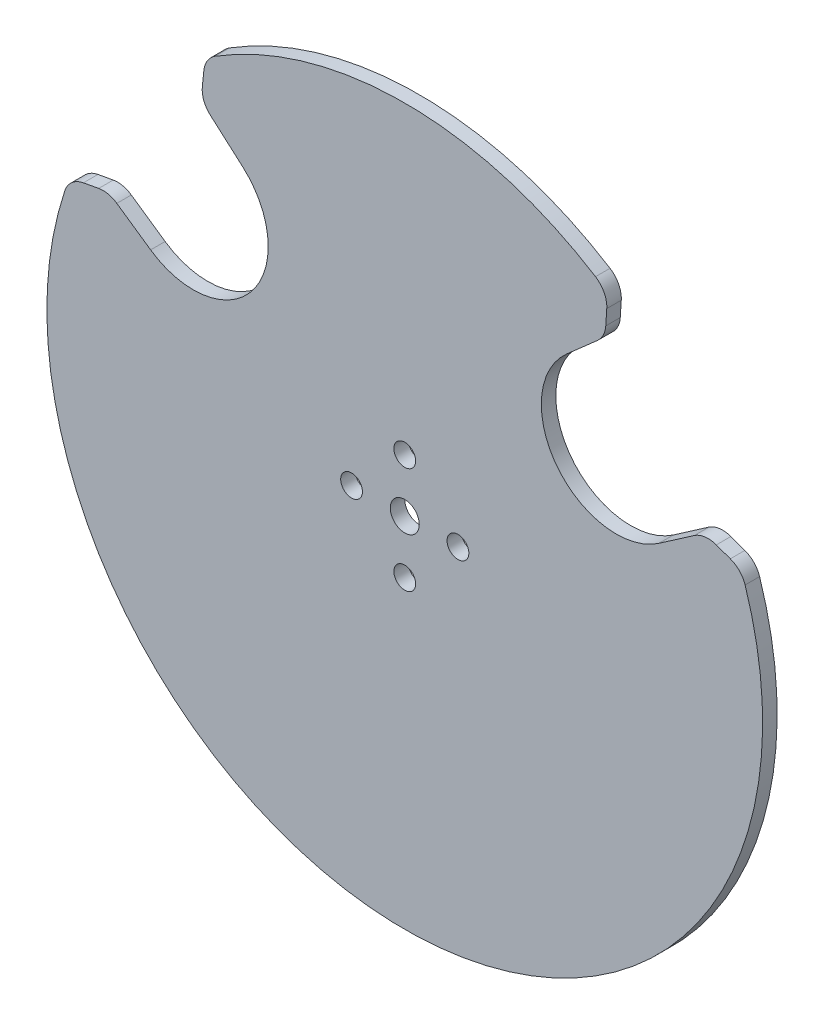
SolidWorks part; units mm, degrees
material "Contreplaqué pin"
ref_plane "Plan de face" through (0, 0, 0) normal (0, 0, 1) x (1, 0, 0)
ref_plane "Plan de dessus" through (0, 0, 0) normal (0, 1, 0) x (1, 0, 0)
ref_plane "Plan de droite" through (0, 0, 0) normal (1, 0, 0) x (0, 0, -1)
sketch "Esquisse1" plane through (0, 0, 0) normal (0, 0, 1) x (1, 0, 0)
  line L0 (0, 0) -> (-43.7346, 34.1692) construction
  line L1 (67.0032, 31.4098) -> (52.5476, 21.4185)
  line L2 (0, 0) -> (0, 74) construction
  line L3 (-43.7346, 34.1692) -> (-58.3128, 45.5589) construction
  line L4 (-46.6863, 57.4142) -> (-33.4947, 45.8051)
  line L5 (-67.0032, 31.4098) -> (-52.5476, 21.4185)
  line L6 (46.6863, 57.4142) -> (33.4947, 45.8051)
  arc A0 (-67.0032, 31.4098) -> (67.0032, 31.4098) centre (0, 0) ccw
  circle A1 centre (0, 0) radius 11 construction
  circle A2 centre (0, 11) radius 2.25
  circle A3 centre (11, 0) radius 2.25
  circle A4 centre (0, -11) radius 2.25
  circle A5 centre (-11, 0) radius 2.25
  arc A7 (-52.5476, 21.4185) -> (-33.4947, 45.8051) centre (-43.7346, 34.1692) ccw
  arc A9 (52.5476, 21.4185) -> (33.4947, 45.8051) centre (43.7346, 34.1692) cw
  arc A10 (46.6863, 57.4142) -> (-46.6863, 57.4142) centre (0, 0) ccw
  circle A15 centre (0, 0) radius 3
  point P27 (67.0032, 31.4098)
  point P30 (46.6863, 57.4142)
  point P33 (-46.6863, 57.4142)
  point P36 (-67.0032, 31.4098)
  dimension "D1" = 74
  dimension "D2" = 22
  dimension "D3" = 4.5
  dimension "D6" = 33
  dimension "D4" = 15.5
  dimension "D11" = 6
  dimension "D5" = 52
  dimension "D7" = 18.5
  dimension "D9" = 3.349
  dimension "D10" = 3.349
extrude "Boss.-Extru.1" add sketch "Esquisse1" along normal blind 3
fillet "Congé1" [suppressed] radius 7
chamfer "Chanfrein1" distance 7 angle 45 4 edges at (67.0032, 31.4098, 1.5) (46.6863, 57.4142, 1.5) (-46.6863, 57.4142, 1.5) (-67.0032, 31.4098, 1.5) first distance on face at (0, -21.2951, 1.5) first distance on face at (40.0905, 51.6096, 1.5) first distance on face at (0, 65.7071, 1.5) first distance on face at (-59.7754, 26.4141, 1.5)
fillet "Congé2" radius 5 8 edges at (-41.2993, 61.4033, 1.5) (-42.1241, 53.3993, 1.5) (-69.2973, 25.9593, 1.5) (-61.2448, 27.4297, 1.5) (69.5706, 25.2177, 1.5) (62.0038, 27.9544, 1.5) (41.9527, 60.9588, 1.5) (41.4314, 52.7897, 1.5)
